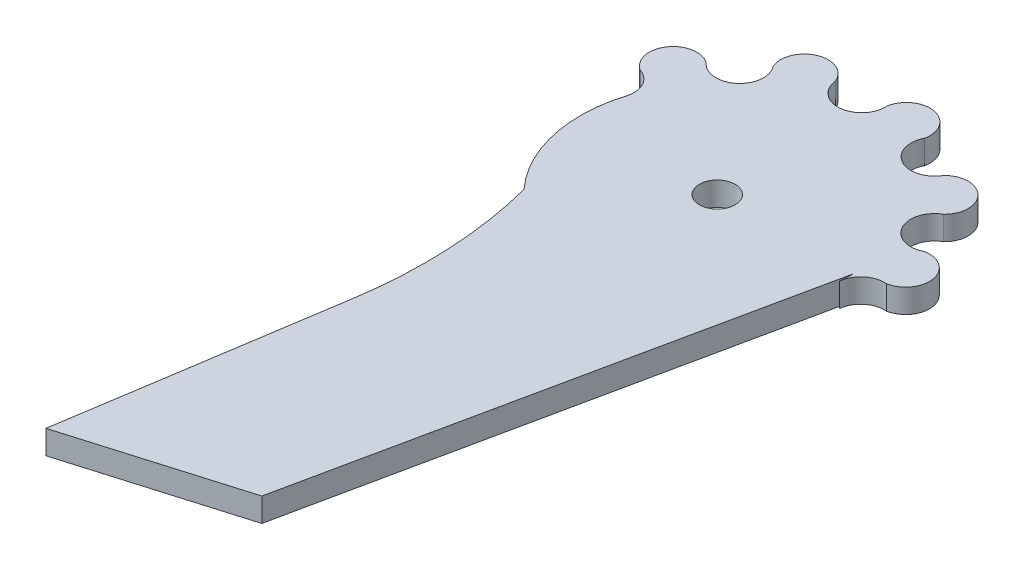
SolidWorks part; units mm, degrees
note: The reader was unsure of these and kept them because the rebuilt part matched: shared geometry of "Sketch1<5>".
ref_plane "Front Plane" through (0, 0, 0) normal (0, 0, 1) x (1, 0, 0)
ref_plane "Top Plane" through (0, 0, 0) normal (0, 1, 0) x (1, 0, 0)
ref_plane "Right Plane" through (0, 0, 0) normal (1, 0, 0) x (0, 0, -1)
sketch "Sketch1" plane through (0, 0, 0) normal (0, 1, 0) x (1, 0, 0)
  line L0 (0, 0) -> (-13.5, 0) construction
  line L1 (0, 0) -> (11.5, 0) construction
  line L2 (11.5, 0) -> (2.8068, -41.0887)
  line L3 (2.8068, -41.0887) -> (-11.192, -45.2316)
  line L4 (-11.192, -45.2316) -> (-7.7384, -22.8541)
  circle A0 centre (0, 0) radius 11.5
  circle A4 centre (-13.5, 0) radius 2
  circle A5 centre (-12.9174, 3.9229) radius 2
  circle A6 centre (-11.2201, 7.5073) radius 2
  circle A7 centre (-8.5544, 10.4438) radius 2
  circle A8 centre (-5.1504, 12.4789) radius 2
  circle A9 centre (-1.3019, 13.4371) radius 2
  circle A10 centre (2.6589, 13.2356) radius 2
  circle A11 centre (6.3903, 11.8918) radius 2
  circle A12 centre (9.5702, 9.5217) radius 2
  circle A13 centre (11.9241, 6.3298) radius 2
  circle A14 centre (13.2489, 2.5917) radius 2
  arc A15 (-7.7384, -22.8541) -> (-8.4958, -7.7505) centre (-44.7626, -17.14) ccw
  circle A16 centre (0, 0) radius 1.5
  circle A17 centre (13.4303, -1.3702) radius 2
  point P3 (0, 0)
  point P34 (-13.5, 0)
  dimension "D1" = 23
  dimension "D2" = 4
  dimension "D4" = 13.5
  dimension "D5" = 3
  dimension "D3" = 12
extrude "Boss-Extrude3" add sketch "Sketch1" along normal mid plane 2
extrude "Boss-Extrude5" add sketch "Sketch1<5>" along normal mid plane 2 contours A15 L4 L3 L2 A0
sketch "Sketch1<5>" plane through (0, 0, 0) normal (0, 1, 0) x (1, 0, 0) same geometry as "Sketch1"
